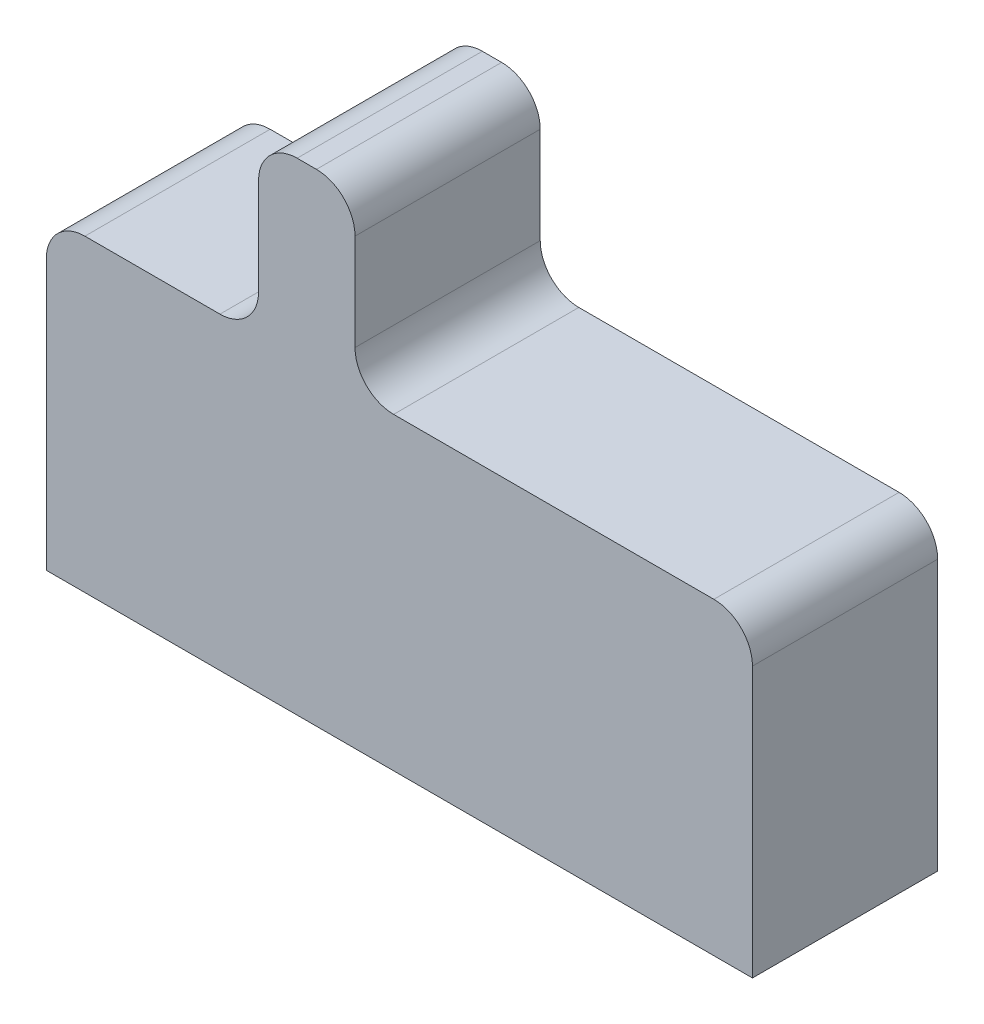
SolidWorks part; units mm, degrees
material "Pure Gold"
ref_plane "Front Plane" through (0, 0, 0) normal (0, 0, 1) x (1, 0, 0)
ref_plane "Top Plane" through (0, 0, 0) normal (0, 1, 0) x (1, 0, 0)
ref_plane "Right Plane" through (0, 0, 0) normal (1, 0, 0) x (0, 0, -1)
sketch "Sketch1" plane through (0, 0, 0) normal (0, 0, 1) x (1, 0, 0)
  line L0 (-0.73, 0.8) -> (-0.73, 1.7)
  line L1 (-1.83, 0.8) -> (-0.73, 0.8)
  line L2 (-1.83, 0.8) -> (-1.83, -0.8)
  line L3 (-1.83, -0.8) -> (1.83, -0.8)
  line L4 (1.83, 0.8) -> (1.83, -0.8)
  line L5 (-1.83, 0.8) -> (1.83, -0.8) construction
  line L6 (-1.83, -0.8) -> (1.83, 0.8) construction
  line L7 (-0.73, 1.7) -> (-0.23, 1.7)
  line L8 (-0.23, 1.7) -> (-0.23, 0.8)
  line L9 (-0.23, 0.8) -> (1.83, 0.8)
  point P0 (0, 0)
  point P8 (-0.48, 1.7)
  dimension "D1" = 3.66
  dimension "D2" = 1.6
  dimension "D3" = 1.35
  dimension "D4" = 0.9
  dimension "D5" = 0.5
extrude "Boss-Extrude1" add sketch "Sketch1" along normal blind 0.96
fillet "Fillet1" radius 0.2 6 edges at (-0.73, 0.8, 0.48) (-0.23, 0.8, 0.48) (-0.23, 1.7, 0.48) (-0.73, 1.7, 0.48) (1.83, 0.8, 0.48) (-1.83, 0.8, 0.48)
equation "\"D4@Sketch1\"=2.5-1.6"
